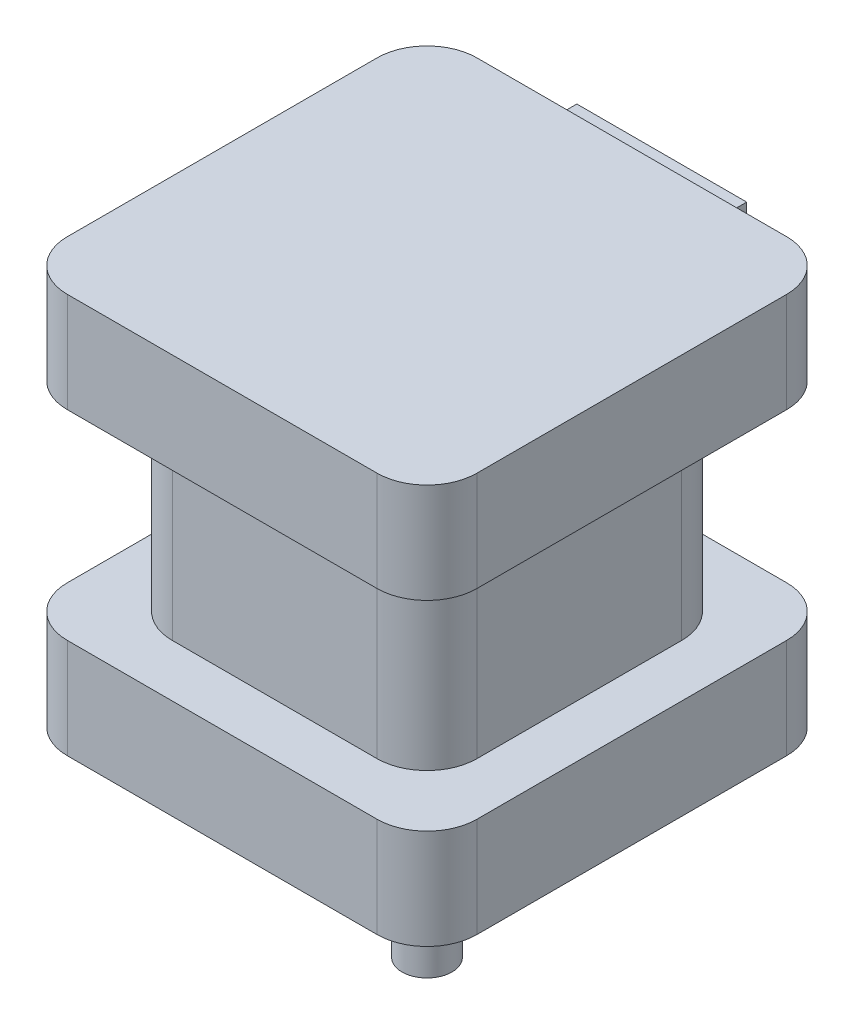
SolidWorks part; units mm, degrees
ref_plane "Front Plane" through (0, 0, 0) normal (0, 0, 1) x (1, 0, 0)
ref_plane "Top Plane" through (0, 0, 0) normal (0, 1, 0) x (1, 0, 0)
ref_plane "Right Plane" through (0, 0, 0) normal (1, 0, 0) x (0, 0, -1)
sketch "Sketch1" plane through (0, 0, 0) normal (0, 1, 0) x (1, 0, 0)
  line L1 (20.5, -20.5) -> (-20.5, -20.5)
  line L2 (20.5, -20.5) -> (20.5, 20.5)
  line L3 (20.5, 20.5) -> (-20.5, 20.5)
  line L4 (-20.5, -20.5) -> (-20.5, 20.5)
  line L5 (20.5, -20.5) -> (-20.5, 20.5) construction
  line L6 (20.5, 20.5) -> (-20.5, -20.5) construction
  line L7 (15.25, -15.25) -> (-15.25, -15.25)
  line L8 (15.25, -15.25) -> (15.25, 15.25)
  line L9 (15.25, 15.25) -> (-15.25, 15.25)
  line L10 (-15.25, -15.25) -> (-15.25, 15.25)
  line L11 (15.25, -15.25) -> (-15.25, 15.25) construction
  line L12 (15.25, 15.25) -> (-15.25, -15.25) construction
  circle A0 centre (0, 0) radius 2.5
  point P0 (0, 0)
  point P6 (0, 0)
  dimension "D5" = 5
  dimension "D1" = 41
  dimension "D2" = 41
  dimension "D3" = 30.5
  dimension "D4" = 30.5
extrude "Boss-Extrude1" add sketch "Sketch1" along normal blind 20 contours A0 region at (0, 0, 0)
extrude "Boss-Extrude2" add sketch "Sketch1<3>" along normal blind 10 from offset 20 separate body contours L4 L1 L2 L3 L7 L10 L9 L8 | L10 L7 L8 L9 A0 region at (0, 0, 19.9202) region at (0, 0, 14.8187)
sketch "Sketch1<3>" plane through (0, 0, 0) normal (0, 1, 0) x (1, 0, 0) same geometry as "Sketch1"
extrude "Boss-Extrude3" add sketch "Sketch1<4>" along normal blind 30 from offset 20 contours L10 L7 L8 L9 A0 region at (0, 0, 14.8187)
sketch "Sketch1<4>" plane through (0, 0, 0) normal (0, 1, 0) x (1, 0, 0) same geometry as "Sketch1"
extrude "Boss-Extrude4" add sketch "Sketch1<5>" along normal blind 10 from offset 50 contours L1 L4 L3 L2
sketch "Sketch1<5>" plane through (0, 0, 0) normal (0, 1, 0) x (1, 0, 0) same geometry as "Sketch1"
fillet "Fillet1" radius 5 12 edges at (-20.5, 25, -20.5) (20.5, 25, -20.5) (20.5, 25, 20.5) (-20.5, 25, 20.5) (15.25, 40, -15.25) (15.25, 40, 15.25) (-15.25, 40, 15.25) (-15.25, 40, -15.25) (-20.5, 55, -20.5) (-20.5, 55, 20.5) (20.5, 55, 20.5) (20.5, 55, -20.5)
sketch "Sketch2" plane through (0, 20, 0) normal (0, -1, 0) x (1, 0, 0)
  line L0 (0, 0) -> (-50000, 0) construction
  line L2 (15.25, 15.25) -> (-15.25, 15.25) construction
  line L3 (15.25, 15.25) -> (15.25, -15.25) construction
  line L4 (-20.5, 15.5) -> (-20.5, -15.5)
  line L5 (-15.5, -20.5) -> (15.5, -20.5)
  line L6 (20.5, -15.5) -> (20.5, 15.5)
  line L7 (15.5, 20.5) -> (-15.5, 20.5)
  line L8 (-20.5, 15.5) -> (-20.5, -15.5)
  line L9 (-15.5, -20.5) -> (15.5, -20.5)
  line L11 (15.5, 20.5) -> (-15.5, 20.5)
  line L12 (15.25, -15.25) -> (-15.25, -15.25) construction
  line L14 (20.5, -15.5) -> (20.5, 15.5)
  line L15 (-15.25, 15.25) -> (-15.25, -15.25) construction
  line L16 (15.25, 15.25) -> (-15.25, -15.25) construction
  line L17 (15.25, -15.25) -> (-15.25, 15.25) construction
  arc A4 (-20.5, -15.5) -> (-15.5, -20.5) centre (-15.5, -15.5) ccw
  arc A5 (15.5, -20.5) -> (20.5, -15.5) centre (15.5, -15.5) ccw
  arc A7 (-15.5, 20.5) -> (-20.5, 15.5) centre (-15.5, 15.5) ccw
  arc A8 (-20.5, -15.5) -> (-15.5, -20.5) centre (-15.5, -15.5) ccw
  arc A11 (-15.5, 20.5) -> (-20.5, 15.5) centre (-15.5, 15.5) ccw
  circle A12 centre (15.25, -15.25) radius 1.75
  arc A14 (-20.5, -15.5) -> (-15.5, -20.5) centre (-15.5, -15.5) ccw construction
  circle A15 centre (-15.25, -15.25) radius 1.75
  circle A16 centre (-15.25, 15.25) radius 1.75
  arc A17 (15.5, -20.5) -> (20.5, -15.5) centre (15.5, -15.5) ccw
  arc A19 (20.5, 15.5) -> (15.5, 20.5) centre (15.5, 15.5) ccw
  arc A20 (20.5, 15.5) -> (15.5, 20.5) centre (15.5, 15.5) ccw
  circle A21 centre (15.25, 15.25) radius 1.75
  point P22 (0, 0)
  dimension "D2" = 30.5
  dimension "D5" = 2
  dimension "D3" = 30.5
  dimension "D4" = 2
  dimension "D1" = 0
extrude "Cut-Extrude1" cut sketch "Sketch2" against normal blind 8 contours A15 | A12 region at (15.25, 20, -15.25) region at (-15.25, 20, -15.25)
mirror "Mirror1" about plane through (0, 0, 0) normal (0, 0, 1) of "Cut-Extrude1"
sketch "Sketch3" plane through (0, 20, 0) normal (0, -1, 0) x (1, 0, 0)
  circle A0 centre (0, 0) radius 13
  dimension "D1" = 26
extrude "Boss-Extrude5" add sketch "Sketch3" along normal blind 4
chamfer "Chamfer1" distance 1 angle 45 1 edges at (0, 16, -13)
sketch "Sketch4" plane through (0, 0, -20.5) normal (0, 0, 1) x (1, 0, 0)
  line L0 (15.5, 55) -> (-15.5, 55) construction
  line L1 (15.5, 50) -> (15.5, 60) construction
  line L2 (-15.5, 60) -> (-15.5, 50) construction
  line L4 (7.5, 53) -> (-7.5, 53)
  line L5 (7.5, 53) -> (7.5, 57)
  line L6 (7.5, 57) -> (-7.5, 57)
  line L7 (-7.5, 53) -> (-7.5, 57)
  line L8 (7.5, 53) -> (-7.5, 57) construction
  line L9 (7.5, 57) -> (-7.5, 53) construction
  point P6 (0, 55)
  dimension "D1" = 15
  dimension "D2" = 4
extrude "Extrude-Thin1" add sketch "Sketch4" against normal blind 3 thin thin type one direction wall 1
